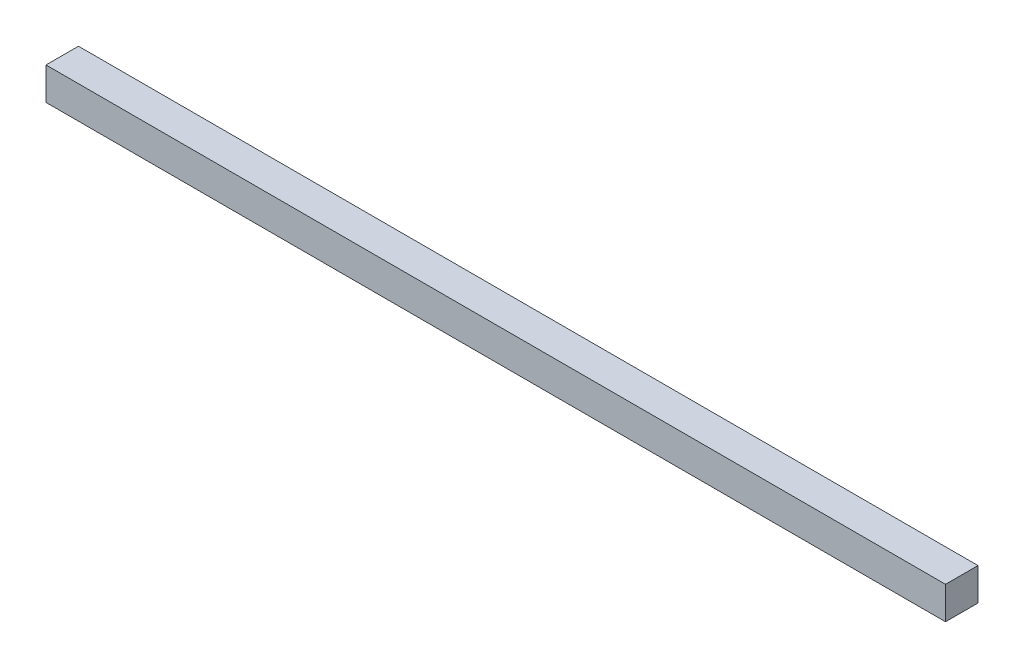
SolidWorks part; units mm, degrees
ref_plane "Plan de face" through (0, 0, 0) normal (0, 0, 1) x (1, 0, 0)
ref_plane "Plan de dessus" through (0, 0, 0) normal (0, 1, 0) x (1, 0, 0)
ref_plane "Plan de droite" through (0, 0, 0) normal (1, 0, 0) x (0, 0, -1)
sketch "Esquisse1" plane through (0, 0, 0) normal (0, 0, 1) x (1, 0, 0)
  line L1 (-116.2232, 39.186) -> (160.7768, 39.186)
  line L2 (-116.2232, 39.186) -> (-116.2232, 29.186)
  line L3 (-116.2232, 29.186) -> (160.7768, 29.186)
  line L4 (160.7768, 39.186) -> (160.7768, 29.186)
  dimension "D1" = 10
  dimension "D2" = 277
extrude "Boss.-Extru.1" add sketch "Esquisse1" along normal blind 10
equation "\"EpaisseurPlaque\"= 3"
equation "\"ProfondeurBoite\"=460"
equation "\"LongueurSyphon\"=170"
equation "\"LargeurSyphon\"=120"
equation "\"HauteurCoteDroit\"= 490"
equation "\"HauteurCoteGauche\"= 540"
equation "\"HauteurSolSyphon\"= 300"
equation "\"HauteurSyphon\"=\"HauteurCoteGauche\"-\"HauteurSolSyphon\""
equation "\"LargeurDroite\"=10"
equation "\"LargeurGauche\"=150"
equation "\"LargeurBoite\"= \"LargeurDroite\" + \"LargeurGauche\" + \"LargeurSyphon\""
equation "\"D2@Esquisse1\"=\"ProfondeurBoite\" - \"LongueurSyphon\" -13"
